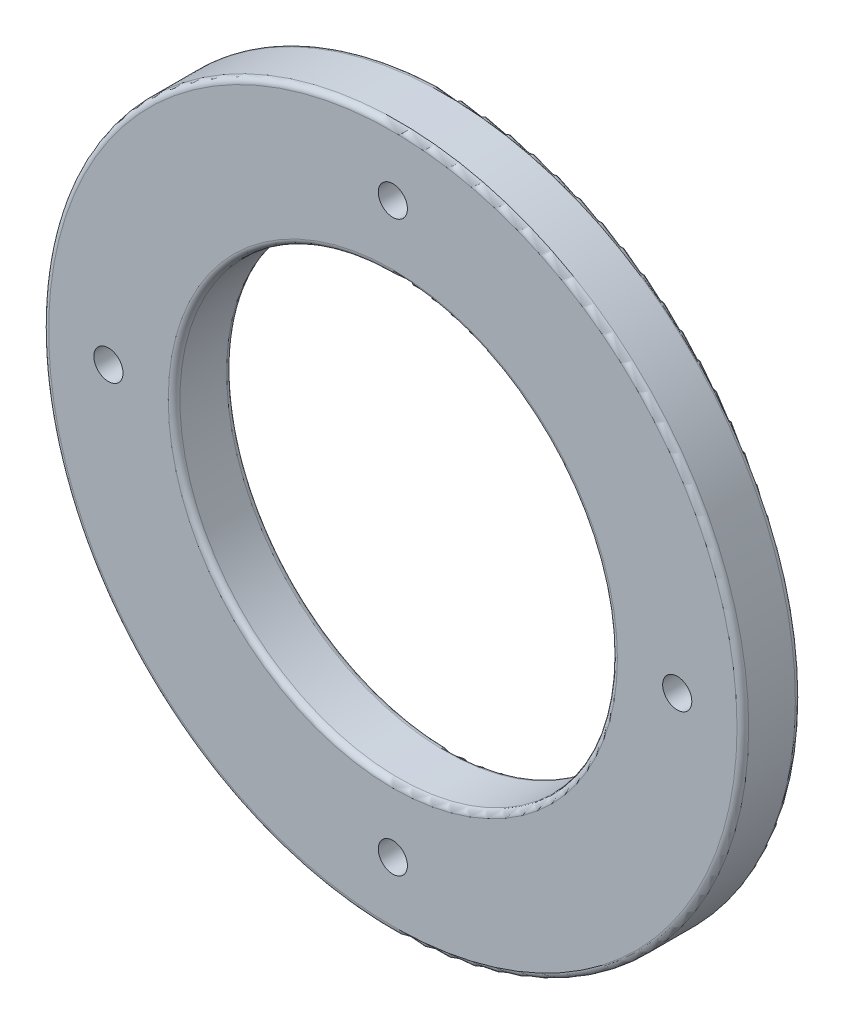
SolidWorks part; units mm, degrees
ref_plane "Front Plane" through (0, 0, 0) normal (0, 0, 1) x (1, 0, 0)
ref_plane "Top Plane" through (0, 0, 0) normal (0, 1, 0) x (1, 0, 0)
ref_plane "Right Plane" through (0, 0, 0) normal (1, 0, 0) x (0, 0, -1)
sketch "Sketch1" plane through (0, 0, 0) normal (0, 0, 1) x (1, 0, 0)
  circle A0 centre (0, 0) radius 76.2
extrude "Boss-Extrude1" add sketch "Sketch1" along normal blind 12.7 contours A0
fillet "Fillet1" radius 1.27 2 edges at (76.2, 0, 0) (76.2, 0, 12.7)
sketch "Sketch2" plane through (0, 0, 12.7) normal (0, 0, 1) x (1, 0, 0)
  circle A0 centre (0, 0) radius 47.625
  circle A1 centre (0, 0) radius 61.9125 construction
  circle A2 centre (0, 61.9125) radius 3.175
  circle A3 centre (61.9125, 0) radius 3.175
  circle A4 centre (0, -61.9125) radius 3.175
  circle A5 centre (-61.9125, 0) radius 3.175
  point P15 (0, 0)
  dimension "D1" = 95.25
  dimension "D2" = 123.825
  dimension "D3" = 4
extrude "Cut-Extrude1" cut sketch "Sketch2" against normal blind 12.7
fillet "Fillet2" radius 1.27 2 edges at (47.625, 0, 0) (47.625, 0, 12.7)
